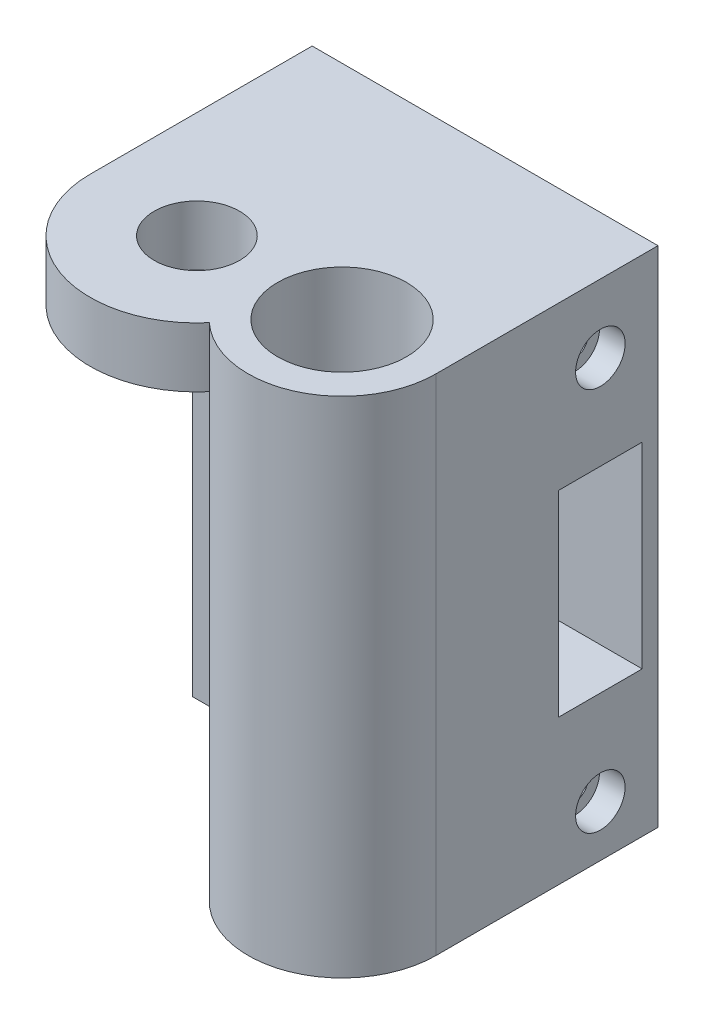
SolidWorks part; units mm, degrees
ref_plane "Alzado" through (0, 0, 0) normal (0, 0, 1) x (1, 0, 0)
ref_plane "Planta" through (0, 0, 0) normal (0, 1, 0) x (1, 0, 0)
ref_plane "Vista lateral" through (0, 0, 0) normal (1, 0, 0) x (0, 0, -1)
sketch "Croquis1" plane through (0, 0, 0) normal (0, 1, 0) x (1, 0, 0)
  line L0 (28, 0) -> (28, 26)
  line L1 (-12.5, 0) -> (-12.5, 26)
  line L2 (-12.5, 26) -> (28, 26)
  circle A0 centre (0, 0) radius 5
  circle A1 centre (17, 0) radius 7.55
  arc A2 (-12.5, 0) -> (9.5368, -8.0808) centre (0, 0) ccw
  arc A3 (9.5368, -8.0808) -> (28, 0) centre (17, 0) ccw
  dimension "D1" = 10
  dimension "D2" = 15.1
  dimension "D4" = 25
  dimension "D5" = 22
  dimension "D3" = 17
  dimension "D6" = 26
extrude "Saliente-Extruir1" add sketch "Croquis1" along normal blind 7
sketch "Croquis4" plane through (0, 0, 0) normal (0, -1, 0) x (1, 0, 0)
  line L1 (28, 0) -> (28, -26) construction
  line L2 (-12.5, -26) -> (28, -26)
  line L3 (28, 0) -> (28, -26)
  line L4 (6, 0) -> (6, -12)
  line L5 (-12.5, -12) -> (6, -12)
  line L6 (-12.5, -26) -> (-12.5, 0) construction
  arc A0 (28, 0) -> (9.5368, 8.0808) centre (17, 0) ccw construction
  arc A1 (28, 0) -> (9.5368, 8.0808) centre (17, 0) ccw
  arc A2 (28, 0) -> (6, 0) centre (17, 0) ccw
  circle A3 centre (17, 0) radius 7.55
  arc M1 (28, 0) -> (9.5368, 8.0808) centre (17, 0) ccw
  line M3 (-12.5, 0) -> (-12.5, -26)
  line M4 (-12.5, -26) -> (28, -26)
  line M5 (28, -26) -> (28, 0)
  circle M7 centre (17, 0) radius 7.55
  dimension "D1" = 15.1
  dimension "D2" = 14
extrude "Saliente-Extruir4" add sketch "Croquis4" along normal blind 52 contours A2 L4 L5 M1 M3 M4 M5 M7 region at (10.771, 0, -13.6221)
sketch "Croquis5" plane through (-12.5, 0, 0) normal (-1, 0, 0) x (0, 0, 1)
  line L0 (-26, 7) -> (-26, -52) construction
  line L1 (-26, 7) -> (0, 7) construction
  circle A0 centre (-19.25, -1) radius 4.1
  circle A1 centre (-19.25, -46) radius 4.1
  dimension "D1" = 8.2
  dimension "D2" = 8.2
  dimension "D3" = 45
  dimension "D4" = 6.75
  dimension "D5" = 8
extrude "Cortar-Extruir1" cut sketch "Croquis5" against normal blind 35
sketch "Croquis6" plane through (-12.5, 0, 0) normal (-1, 0, 0) x (0, 0, 1)
  line L0 (-26, 7) -> (-26, -52) construction
  line L1 (-24.15, -35) -> (-14.35, -35)
  line L2 (-24.15, -35) -> (-24.15, -12)
  line L3 (-24.15, -12) -> (-14.35, -12)
  line L4 (-14.35, -35) -> (-14.35, -12)
  line L5 (-24.15, -35) -> (-14.35, -12) construction
  line L6 (-24.15, -12) -> (-14.35, -35) construction
  circle A0 centre (-19.25, -1) radius 4.1 construction
  circle A1 centre (-19.25, -1) radius 4.1 construction
  point P0 (-19.25, -23.5)
  dimension "D1" = 9.8
  dimension "D2" = 23
  dimension "D3" = 6.75
  dimension "D4" = 22.5
extrude "Cortar-Extruir2" cut sketch "Croquis6" against normal through all
sketch "Croquis7" plane through (28, 0, 0) normal (1, 0, 0) x (0, 0, -1)
  circle A0 centre (19.25, -1) radius 4.1 construction
  circle A1 centre (19.25, -1) radius 4.1 construction
  circle A2 centre (19.25, -46) radius 4.1 construction
  circle A3 centre (19.25, -46) radius 4.1 construction
  circle A4 centre (19.25, -1) radius 1.55
  circle A5 centre (19.25, -46) radius 1.55
  dimension "D1" = 3.1
  dimension "D2" = 3.1
extrude "Cortar-Extruir3" cut sketch "Croquis7" against normal through all
sketch "Croquis8" plane through (28, 0, 0) normal (1, 0, 0) x (0, 0, -1)
  circle A0 centre (19.25, -1) radius 1.55 construction
  circle A1 centre (19.25, -1) radius 1.55
  circle A2 centre (19.25, -46) radius 1.55 construction
  circle A3 centre (19.25, -46) radius 1.55
  circle A4 centre (19.25, -1) radius 2.9
  circle A5 centre (19.25, -46) radius 2.9
  dimension "D1" = 5.8
  dimension "D2" = 5.8
extrude "Cortar-Extruir4" cut sketch "Croquis8" against normal blind 3
sketch "Croquis10" plane through (0, 0, -12) normal (0, 0, 1) x (1, 0, 0)
  line L0 (-12.5, -52) -> (6, -52) construction
  line L1 (-12.5, -52) -> (-12.5, 0) construction
  circle A0 centre (-5.5, -23.5) radius 1.5
  point P4 (-3.25, -52)
  dimension "D1" = 3
  dimension "D2" = 28.5
  dimension "D3" = 7
extrude "Cortar-Extruir5" cut sketch "Croquis10" against normal through all
